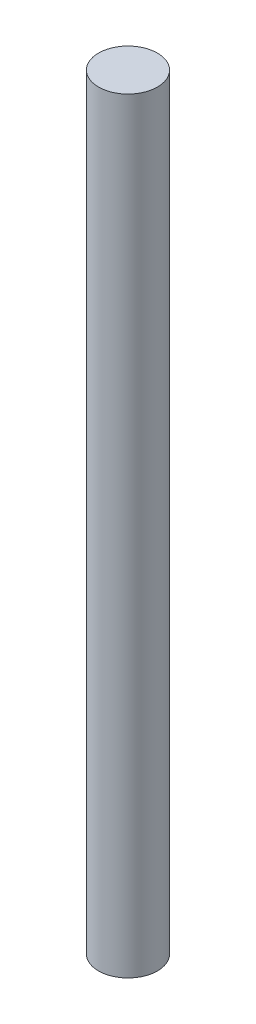
SolidWorks part; units mm, degrees
material "AISI 316 Annealed Stainless Steel Bar (SS)"
ref_plane "Front Plane" through (0, 0, 0) normal (0, 0, 1) x (1, 0, 0)
ref_plane "Top Plane" through (0, 0, 0) normal (0, 1, 0) x (1, 0, 0)
ref_plane "Right Plane" through (0, 0, 0) normal (1, 0, 0) x (0, 0, -1)
sketch "Sketch1" plane through (0, 0, 0) normal (0, 1, 0) x (1, 0, 0)
  circle A0 centre (0, 0) radius 6.35
  dimension "D1" = 12.7
extrude "Boss-Extrude1" add sketch "Sketch1" along normal blind 165.1
